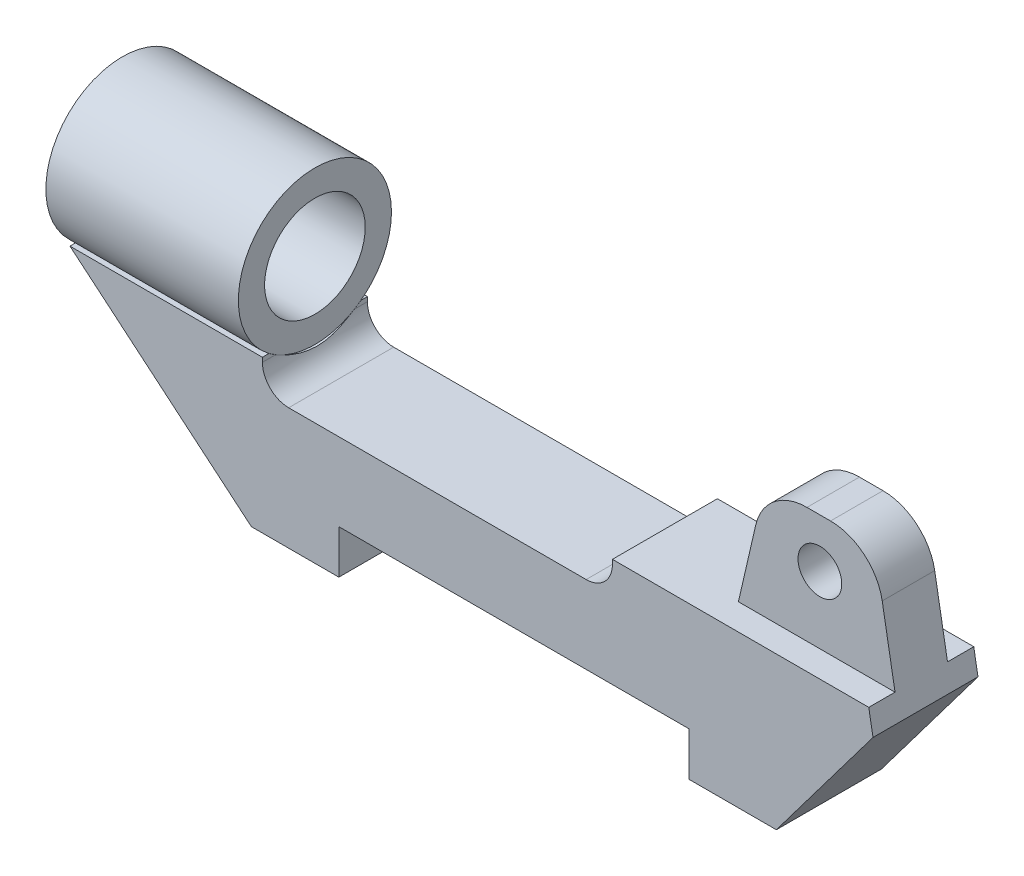
SolidWorks part; units mm, degrees
ref_plane "Front Plane" through (0, 0, 0) normal (0, 0, 1) x (1, 0, 0)
ref_plane "Top Plane" through (0, 0, 0) normal (0, 1, 0) x (1, 0, 0)
ref_plane "Right Plane" through (0, 0, 0) normal (1, 0, 0) x (0, 0, -1)
sketch "Sketch1" plane through (0, 0, 0) normal (0, 0, 1) x (1, 0, 0)
  line L0 (-30, 0) -> (30, 0) construction
  line L1 (30, 0) -> (41.0456, 14.658)
  line L2 (41.0456, 14.658) -> (38.2243, 30.658)
  line L3 (38.2243, 30.658) -> (25.7243, 30.658)
  line L4 (25.7243, 30.658) -> (22.6635, 17.4)
  line L5 (22.6635, 17.4) -> (11.2635, 17.4)
  line L6 (11.2635, 17.4) -> (11.2635, 13.9)
  line L7 (11.2635, 13.9) -> (-28.7365, 13.9)
  line L8 (-28.7365, 13.9) -> (-28.7365, 17.4)
  line L9 (-28.7365, 17.4) -> (-50.7365, 17.4)
  line L10 (-50.7365, 17.4) -> (-30, 0)
  line L11 (-20, 0) -> (-30, 0)
  line L13 (-20, 0) -> (-20, 5)
  line L14 (-20, 5) -> (20, 5)
  line L15 (20, 0) -> (20, 5)
  line L16 (20, 0) -> (30, 0)
  line L17 (22.6635, 17.4) -> (40.5621, 17.4)
  circle A0 centre (31.9743, 25.058) radius 2.5
  point P3 (0, 0)
  point P20 (0, 0)
  point P21 (31.9743, 30.658)
  point P22 (0, 5)
  dimension "D15" = 5
  dimension "D1" = 60
  dimension "D2" = 127
  dimension "D3" = 140
  dimension "D4" = 17.4
  dimension "D5" = 22
  dimension "D6" = 40
  dimension "D7" = 11.4
  dimension "D8" = 12.5
  dimension "D9" = 3.5
  dimension "D10" = 133
  dimension "D11" = 103
  dimension "D12" = 16
  dimension "D13" = 40
  dimension "D14" = 5
  dimension "D16" = 5.6
extrude "Boss-Extrude1" add sketch "Sketch1" along normal mid plane 12 contours L17 L5 L6 L7 L8 L9 L10 L11 L13 L14 L15 L16 L1 L2 region at (-1.6691, 9.7993, 0)
extrude "Boss-Extrude2" add sketch "Sketch1<3>" along normal mid plane 6 contours L4 L17 L2 L3 A0 region at (31.6128, 17.6227, 0)
sketch "Sketch1<3>" plane through (0, 0, 0) normal (0, 0, 1) x (1, 0, 0) same geometry as "Sketch1"
fillet "Fillet1" radius 3 2 edges at (11.2635, 13.9, 0) (-28.7365, 13.9, 0)
fillet "Fillet2" radius 6 2 edges at (25.7243, 30.658, 0) (38.2243, 30.658, 0)
sketch "Sketch2" plane through (-28.7365, 0, 0) normal (1, 0, 0) x (0, 0, -1)
  line L0 (-6, 17.4) -> (6, 17.4) construction
  circle A0 centre (0, 24.4) radius 8.75
  point P5 (0, 0)
  dimension "D1" = 17.5
  dimension "D2" = 7
extrude "Cut-Extrude1" cut sketch "Sketch2" against normal up to vertex (22 mm away) and the other way blind 6 up to point (-50.7365, 17.4, 6)
extrude "Extrude-Thin4" add sketch "Sketch2<5>" against normal up to vertex (22 mm away) separate body thin contours A0 up to point (-50.7365, 17.4, 6) thin type one direction reverse wall 3
sketch "Sketch2<5>" plane through (-28.7365, 0, 0) normal (1, 0, 0) x (0, 0, -1) same geometry as "Sketch2"
